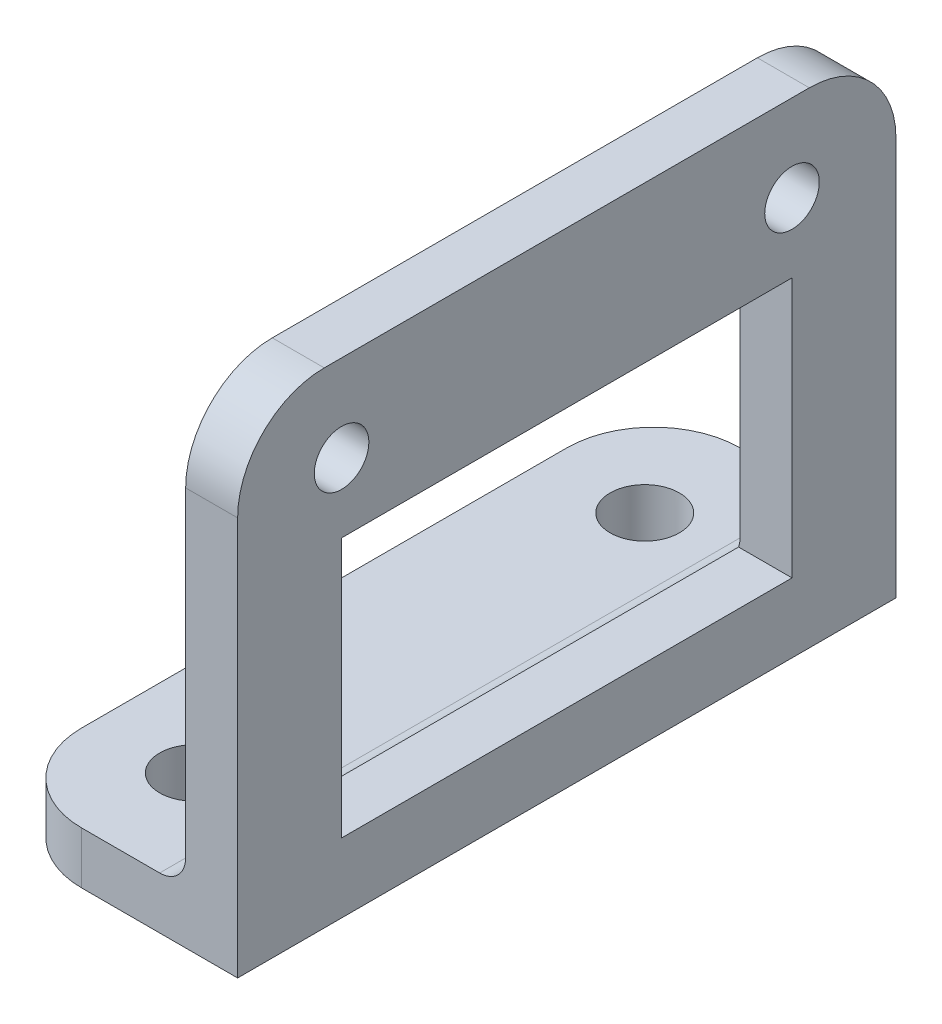
SolidWorks part; units mm, degrees
ref_plane "Front Plane" through (0, 0, 0) normal (0, 0, 1) x (1, 0, 0)
ref_plane "Top Plane" through (0, 0, 0) normal (0, 1, 0) x (1, 0, 0)
ref_plane "Right Plane" through (0, 0, 0) normal (1, 0, 0) x (0, 0, -1)
sketch "Sketch1" plane through (0, 0, 0) normal (0, 0, 1) x (1, 0, 0)
  line L1 (0, 0) -> (4, 0)
  line L2 (1, 3) -> (1, 28)
  line L3 (1, 28) -> (4, 28)
  line L4 (4, 0) -> (4, 28)
  line L5 (0, 0) -> (-10, 0)
  line L7 (1, 3) -> (-10, 3)
  line L8 (-10, 0) -> (-10, 3)
  dimension "D1" = 28
  dimension "D2" = 10
  dimension "D3" = 4
  dimension "D4" = 3
  dimension "D5" = 3
extrude "Boss-Extrude1" add sketch "Sketch1" along normal mid plane 38
sketch "Sketch2" plane through (0, 3, 0) normal (0, 1, 0) x (1, 0, 0)
  line L0 (1, 0) -> (-10, 0) construction
  line L1 (-10, -19) -> (-10, 19) construction
  line L2 (1, -19) -> (1, 19) construction
  circle A0 centre (-4.5, 13) radius 2
  circle A1 centre (-4.5, -13) radius 2
  point P8 (-4.5, 0)
  dimension "D1" = 4
  dimension "D2" = 13
extrude "Cut-Extrude1" cut sketch "Sketch2" against normal through all and the other way through all
sketch "Sketch3" plane through (1, 0, 0) normal (-1, 0, 0) x (0, 0, 1)
  line L0 (0, 28) -> (0, 3) construction
  line L1 (19, 28) -> (-19, 28) construction
  line L2 (19, 3) -> (-19, 3) construction
  line L4 (-13, 4) -> (13, 4)
  line L5 (-13, 4) -> (-13, 19)
  line L6 (-13, 19) -> (13, 19)
  line L7 (13, 4) -> (13, 19)
  line L8 (0, 19) -> (0, 4) construction
  line L9 (-13, 11.5) -> (13, 11.5) construction
  circle A0 centre (-13, 23) radius 1.575
  circle A1 centre (13, 23) radius 1.575
  point P10 (0, 11.5)
  dimension "D1" = 3.15
  dimension "D3" = 20
  dimension "D2" = 13
  dimension "D4" = 15
  dimension "D5" = 4
extrude "Cut-Extrude2" cut sketch "Sketch3" against normal through all
fillet "Fillet1" radius 1.5 1 edges at (1, 3, 0)
fillet "Fillet2" radius 5 4 edges at (2.5, 28, -19) (-10, 1.5, -19) (-10, 1.5, 19) (2.5, 28, 19)
